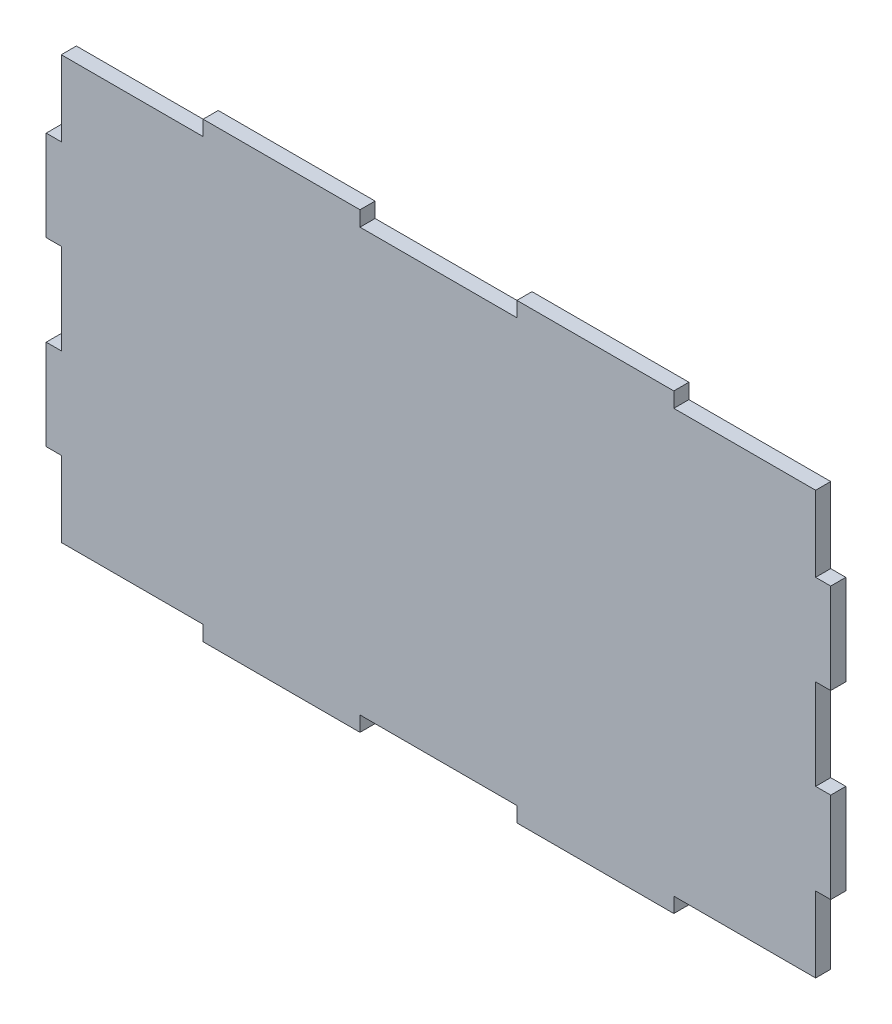
SolidWorks part; units mm, degrees
ref_plane "Alzado" through (0, 0, 0) normal (0, 0, 1) x (1, 0, 0)
ref_plane "Planta" through (0, 0, 0) normal (0, 1, 0) x (1, 0, 0)
ref_plane "Vista lateral" through (0, 0, 0) normal (1, 0, 0) x (0, 0, -1)
sketch "Croquis1" plane through (0, 0, 0) normal (0, 0, 1) x (1, 0, 0)
  line L0 (130, 150) -> (130, 129.9372) construction
  line L1 (52, 0) -> (104, 0)
  line L2 (0, 30) -> (0, 60)
  line L3 (52, 150) -> (104, 150)
  line L4 (260, 30) -> (260, 60)
  line L5 (0, 75) -> (16.5526, 75) construction
  line L6 (0, 120) -> (5, 120)
  line L7 (0, 90) -> (0, 120)
  line L8 (5, 90) -> (0, 90)
  line L9 (0, 30) -> (5, 30)
  line L10 (0, 0) -> (5, 0) construction
  line L11 (5, 60) -> (0, 60)
  line L12 (5, 30) -> (5, 5)
  line L13 (5, 60) -> (5, 90)
  line L14 (5, 120) -> (5, 145)
  line L15 (0, 30) -> (0, 0) construction
  line L16 (255, 30) -> (255, 5)
  line L17 (260, 30) -> (255, 30)
  line L18 (255, 60) -> (260, 60)
  line L19 (255, 60) -> (255, 90)
  line L20 (255, 90) -> (260, 90)
  line L21 (260, 120) -> (255, 120)
  line L22 (255, 120) -> (255, 145)
  line L23 (260, 90) -> (260, 120)
  line L24 (52, 150) -> (52, 145)
  line L25 (208, 5) -> (255, 5)
  line L26 (104, 145) -> (104, 150)
  line L27 (208, 150) -> (208, 145)
  line L28 (156, 145) -> (156, 150)
  line L29 (208, 0) -> (208, 5)
  line L30 (52, 145) -> (5, 145)
  line L31 (104, 145) -> (156, 145)
  line L32 (208, 145) -> (255, 145)
  line L33 (156, 150) -> (208, 150)
  line L34 (156, 5) -> (156, 0)
  line L35 (104, 5) -> (156, 5)
  line L36 (104, 5) -> (104, 0)
  line L37 (52, 0) -> (52, 5)
  line L38 (52, 5) -> (5, 5)
  line L39 (156, 0) -> (208, 0)
  line L40 (0, 0) -> (52, 0) construction
  dimension "D1" = 5
  dimension "D2" = 260
  dimension "D3" = 5
  dimension "D4" = 30
  dimension "D5" = 30
  dimension "D6" = 52
  dimension "D7" = 52
  dimension "D8" = 5
  dimension "D9" = 150
  dimension "D10" = 52
  dimension "D11" = 25
extrude "Saliente-Extruir1" add sketch "Croquis1" along normal blind 5
